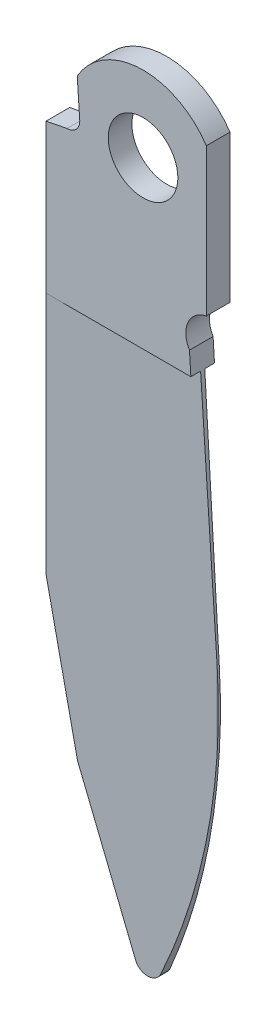
SolidWorks part; units mm, degrees
material "AISI 1045 Steel, cold drawn"
ref_plane "Front Plane" through (0, 0, 0) normal (0, 0, 1) x (1, 0, 0)
ref_plane "Top Plane" through (0, 0, 0) normal (0, 1, 0) x (1, 0, 0)
ref_plane "Right Plane" through (0, 0, 0) normal (1, 0, 0) x (0, 0, -1)
sketch "Sketch1" plane through (0, 0, 0) normal (0, 0, 1) x (1, 0, 0)
  line L0 (18.0689, 40.6551) -> (90.3446, 40.6551) construction
  line L1 (55.1292, 58.6467) -> (55.1292, 35.0247)
  line L2 (55.1292, 35.0247) -> (56.9072, 26.1347)
  line L3 (56.9072, 26.1347) -> (60.1899, 17.2447)
  line L9 (64.7812, 34.7707) -> (63.7652, 51.0267)
  line L12 (64.7812, 53.3127) -> (64.7812, 62.1899)
  line L13 (55.1292, 58.6467) -> (56.3992, 58.9007)
  line L14 (57.0088, 61.9436) -> (57.1612, 59.6627)
  arc A1 (56.3992, 58.9007) -> (57.1612, 59.6627) centre (56.3992, 59.6627) ccw
  arc A3 (64.7812, 62.1899) -> (57.0088, 61.9436) centre (60.9712, 59.6627) ccw
  arc A4 (61.6003, 17.1975) -> (64.7812, 34.7707) centre (27.5159, 32.4416) ccw
  arc A5 (60.1899, 17.2447) -> (61.6003, 17.1975) centre (60.9047, 17.5086) ccw
  arc A7 (64.7812, 53.3127) -> (63.7652, 51.0267) centre (65.0688, 51.8161) ccw
  point P4 (0, 0)
  point P10 (0, 0)
  point P13 (0, 0)
  point P14 (61.797, 59.7072)
  point P15 (0, 0)
  point P17 (0, 0)
  point P19 (0, 0)
  point P21 (0, 0)
  point P25 (0, 0)
  point P28 (0, 0)
  point P29 (0, 0)
  point P30 (64.7812, 54.028)
  point P33 (64.4722, 18.7978)
  dimension "D1" = 4.572
  dimension "D5" = 0.762
  dimension "D8" = 6.35
  dimension "D9" = 3.81
  dimension "D11" = 2.794
  dimension "D6" = 1.016
  dimension "D4" = 0.762
  dimension "D10" = 1.524
  dimension "D15" = 37.338
  dimension "D19" = 0.762
  dimension "D2" = 3.9624
  dimension "D3" = 3.81
  dimension "D7" = 5.842
  dimension "D12" = 8.636
  dimension "D13" = 24.892
  dimension "D14" = 3.81
  dimension "D16" = 33.528
  dimension "D17" = 4.064
  dimension "D18" = 42.418
extrude "Boss-Extrude1" add sketch "Sketch1" along normal mid plane 1.4224
sketch "Sketch2" plane through (0, 0, 0.7112) normal (0, 0, 1) x (1, 0, 0)
  circle A0 centre (60.9712, 59.6627) radius 2.0955
  dimension "D1" = 4.191
extrude "Cut-Extrude1" cut sketch "Sketch2" against normal through all
sketch "Sketch3" plane through (0, 0, 0) normal (0, 1, 0) x (1, 0, 0)
  line L0 (64.7812, 0.0635) -> (55.1292, 0.7112)
  line L1 (64.7812, -0.7112) -> (64.7812, 0.7112) construction
  line L2 (55.1292, -0.7112) -> (55.1292, 0.7112) construction
  line L4 (55.1292, 0.7112) -> (64.7812, 0.7112)
  line L5 (64.7812, 0.7112) -> (64.7812, 0.0635)
  line L6 (55.1292, -0.7112) -> (64.7812, -0.0635)
  line L7 (64.7812, -0.0635) -> (64.7812, -0.7112)
  line L8 (55.1292, -0.7112) -> (64.7812, -0.7112)
  line L9 (64.7812, -0.7112) -> (64.7812, 0.7112) construction
  point P1 (0, 0)
  point P6 (0, 0)
  point P10 (64.7812, 0.0872)
  point P19 (0, 0)
  dimension "D1" = 0.127
extrude "Cut-Extrude2" cut sketch "Sketch3" along normal blind 49.6824
sketch "Sketch4" plane through (64.7812, 0, 0) normal (-1, 0, 0) x (0, 0, 1)
  line L10 (0.7112, 30.1125) -> (0.7112, 34.7707) construction
  line L11 (0.7112, 30.1125) -> (0.0635, 30.1125)
  line L12 (0.7112, 30.1125) -> (0.7112, 34.7707)
  line L13 (0.7112, 34.7707) -> (0.0635, 34.7707)
  line L14 (0.0635, 30.1125) -> (0.0635, 34.7707)
  line L15 (0.0635, 30.1125) -> (0.7112, 30.1125) construction
  line L17 (-0.7112, 34.7707) -> (-0.0635, 34.7707)
  line L18 (-0.7112, 34.7707) -> (-0.7112, 30.1125)
  line L19 (-0.7112, 30.1125) -> (-0.0635, 30.1125)
  line L20 (-0.0635, 34.7707) -> (-0.0635, 30.1125)
extrude "Cut-Extrude4" cut sketch "Sketch4" against normal blind 0.1524
